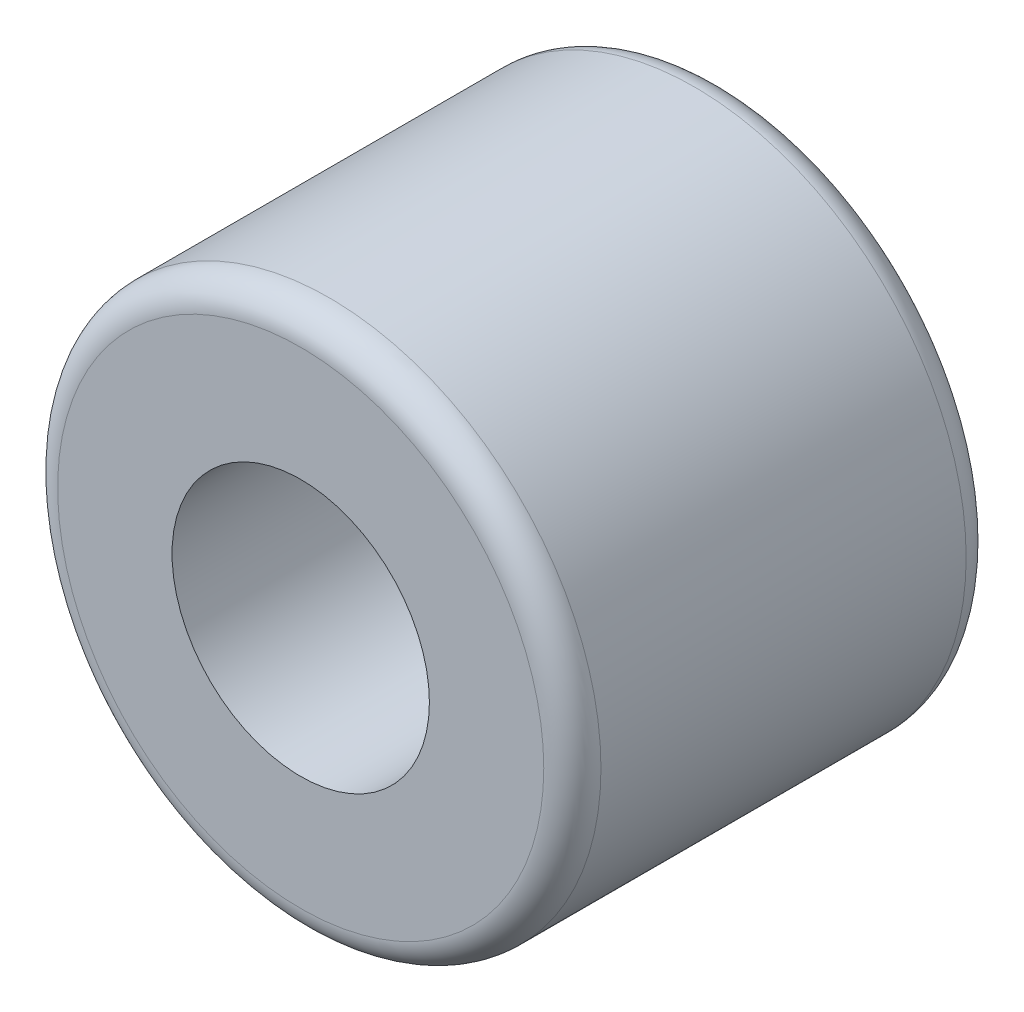
SolidWorks part; units mm, degrees
material "ABS"
ref_plane "Front Plane" through (0, 0, 0) normal (0, 0, 1) x (1, 0, 0)
ref_plane "Top Plane" through (0, 0, 0) normal (0, 1, 0) x (1, 0, 0)
ref_plane "Right Plane" through (0, 0, 0) normal (1, 0, 0) x (0, 0, -1)
sketch "Sketch2" plane through (0, 0, 43.7194) normal (0, 0, 1) x (1, 0, 0)
  circle A0 centre (-51.25, 23.184) radius 4.75
  arc A1 (-47.75, 23.184) -> (-49.5, 26.2151) centre (-51.25, 23.184) ccw construction
  circle A2 centre (-51.25, 23.184) radius 2.25
  dimension "D1" = 4.5
  dimension "D2" = 2.5
extrude "Boss-Extrude1" add sketch "Sketch2" along normal up to surface (7.3856 mm away)
fillet "Fillet1" radius 0.5 2 edges at (-46.5, 23.184, 51.105) (-46.5, 23.184, 43.7194)
